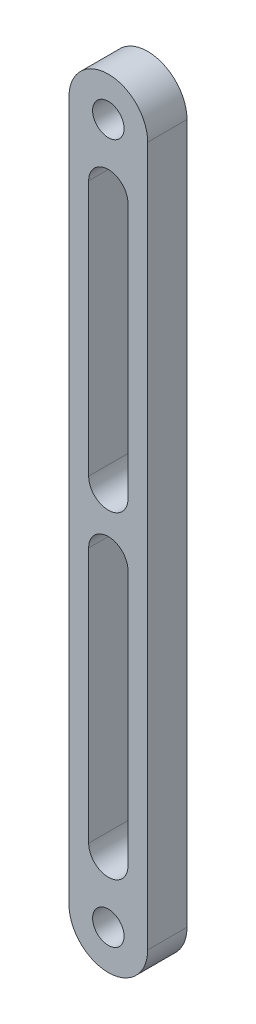
SolidWorks part; units mm, degrees
ref_plane "Front Plane" through (0, 0, 0) normal (0, 0, 1) x (1, 0, 0)
ref_plane "Top Plane" through (0, 0, 0) normal (0, 1, 0) x (1, 0, 0)
ref_plane "Right Plane" through (0, 0, 0) normal (1, 0, 0) x (0, 0, -1)
sketch "Sketch1" plane through (0, 0, 0) normal (0, 0, 1) x (1, 0, 0)
  line L0 (0, -88.9) -> (0, 88.9) construction
  line L1 (-10, -88.9) -> (-10, 88.9)
  line L2 (10, -88.9) -> (10, 88.9)
  line L3 (0, -72.9) -> (0, -7.9) construction
  line L4 (-5, -72.9) -> (-5, -7.9)
  line L5 (5, -72.9) -> (5, -7.9)
  line L6 (0, 72.9) -> (0, 7.9) construction
  line L7 (5, 72.9) -> (5, 7.9)
  line L8 (-5, 72.9) -> (-5, 7.9)
  line L9 (-5, 40.4) -> (5, 40.4) construction
  line L10 (-5, -40.4) -> (5, -40.4) construction
  line L11 (-4, -88.9) -> (-5, -72.9) construction
  line L12 (-4, 88.9) -> (-5, 72.9) construction
  arc A0 (-10, -88.9) -> (10, -88.9) centre (0, -88.9) ccw
  arc A1 (10, 88.9) -> (-10, 88.9) centre (0, 88.9) ccw
  circle A2 centre (0, -88.9) radius 4
  circle A3 centre (0, 88.9) radius 4
  arc A4 (-5, -72.9) -> (5, -72.9) centre (0, -72.9) ccw
  arc A5 (5, -7.9) -> (-5, -7.9) centre (0, -7.9) ccw
  arc A6 (5, 72.9) -> (-5, 72.9) centre (0, 72.9) ccw
  arc A7 (-5, 7.9) -> (5, 7.9) centre (0, 7.9) ccw
  point P2 (0, 0)
  point P14 (0, -40.4)
  point P19 (0, 40.4)
  dimension "D3" = 8
  dimension "D1" = 177.8
  dimension "D2" = 20
  dimension "D4" = 10
  dimension "60" = 65
  dimension "D6" = 16
extrude "Boss-Extrude1" add sketch "Sketch1" along normal blind 10
